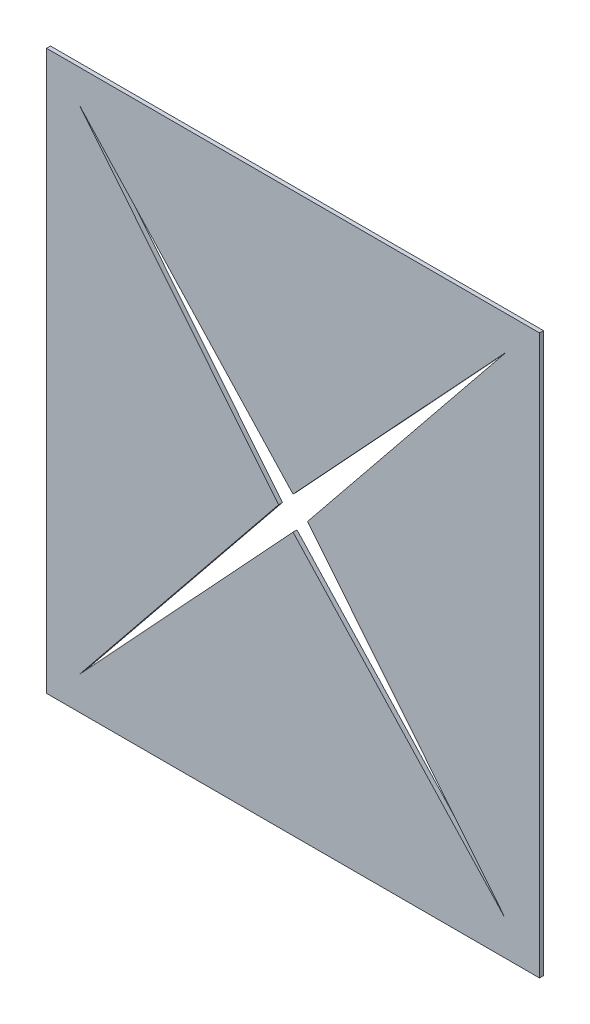
SolidWorks part; units mm, degrees
material "POLYURETHANE (11671)"
ref_plane "Front Plane" through (0, 0, 0) normal (0, 0, 1) x (1, 0, 0)
ref_plane "Top Plane" through (0, 0, 0) normal (0, 1, 0) x (1, 0, 0)
ref_plane "Right Plane" through (0, 0, 0) normal (1, 0, 0) x (0, 0, -1)
sketch "Sketch1" plane through (0, 0, 0) normal (0, 0, 1) x (1, 0, 0)
  line L0 (-41.275, 47.625) -> (-41.275, -47.625)
  line L1 (-47.625, 53.975) -> (47.625, 53.975)
  line L2 (-47.625, 53.975) -> (-47.625, -53.975)
  line L3 (-47.625, -53.975) -> (47.625, -53.975)
  line L4 (47.625, 53.975) -> (47.625, -53.975)
  line L5 (-47.625, 53.975) -> (47.625, -53.975) construction
  line L6 (-47.625, -53.975) -> (47.625, 53.975) construction
  line L7 (-2.8015, 3.175) -> (2.8015, 3.175)
  line L8 (-2.8015, 3.175) -> (-2.8015, -3.175)
  line L9 (-2.8015, -3.175) -> (2.8015, -3.175)
  line L10 (2.8015, 3.175) -> (2.8015, -3.175)
  line L11 (-2.8015, 3.175) -> (2.8015, -3.175) construction
  line L12 (-2.8015, -3.175) -> (2.8015, 3.175) construction
  line L13 (-41.275, -47.625) -> (41.275, -47.625)
  line L14 (41.275, 47.625) -> (41.275, -47.625)
  line L15 (-41.275, 47.625) -> (41.275, 47.625)
  line L16 (41.275, -47.625) -> (0, -3.175)
  line L17 (0, -3.175) -> (-41.275, -47.625)
  line L18 (41.275, -47.625) -> (2.8015, 0)
  line L19 (2.8015, 0) -> (41.275, 47.625)
  line L20 (41.275, 47.625) -> (0, 3.175)
  line L21 (0, 3.175) -> (-41.275, 47.625)
  line L22 (-41.275, 47.625) -> (-2.8015, 0)
  line L23 (-2.8015, 0) -> (-41.275, -47.625)
  point P0 (0, 0)
  point P6 (0, 0)
  dimension "D2" = 95.25
  dimension "D3" = 82.55
  dimension "D4" = 6.35
  dimension "D1" = 6.35
extrude "Boss-Extrude1" add sketch "Sketch1" along normal blind 0.762 contours L4 L1 L2 L3 L0 L15 L14 L13 | L23 L22 L0 | L21 L20 L15 | L19 L18 L14 | L16 L17 L13 region at (-28.4505, 0, 0) region at (0, 32.8083, 0) region at (0, -32.8083, 0) region at (28.4505, 0, 0) region at (0, 52.5354, 0)
